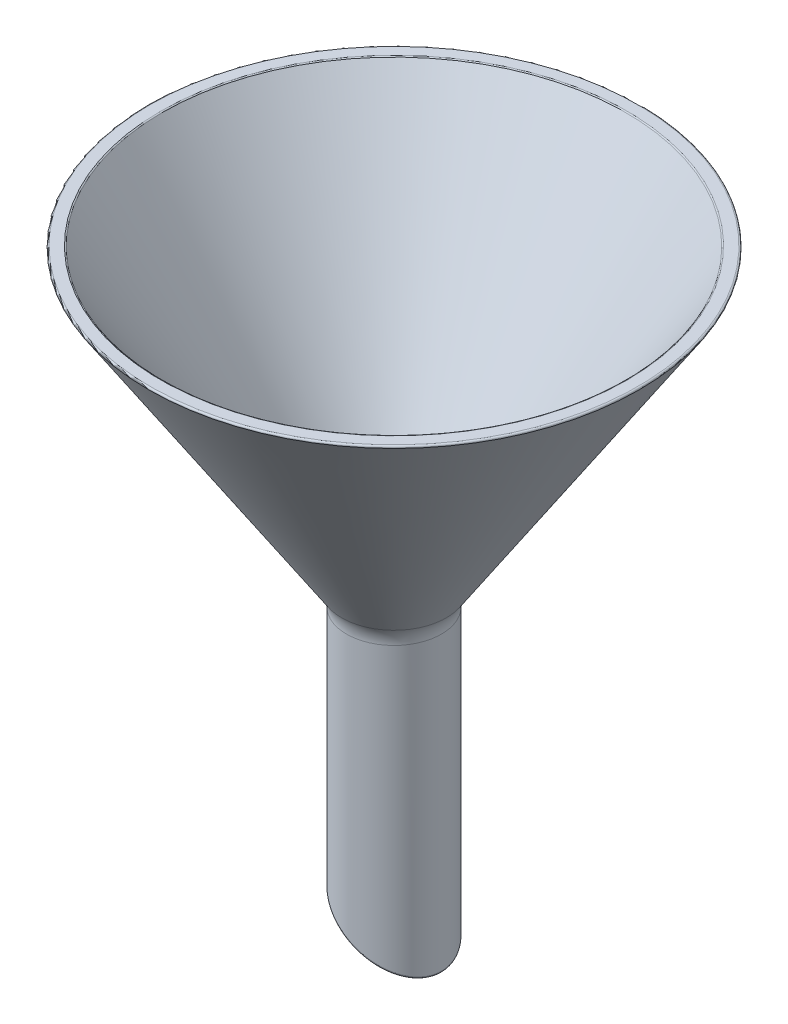
SolidWorks part; units mm, degrees
material "ABS"
ref_plane "Front" through (0, 0, 0) normal (0, 0, 1) x (1, 0, 0)
ref_plane "Top" through (0, 0, 0) normal (0, 1, 0) x (1, 0, 0)
ref_plane "Right" through (0, 0, 0) normal (1, 0, 0) x (0, 0, -1)
sketch "Sketch1" plane through (0, 0, 0) normal (0, 0, 1) x (1, 0, 0)
  line L0 (0, 0) -> (0, -52.07)
  line L1 (0, 0) -> (-20.6375, 0)
  line L2 (-20.6375, 0) -> (-3.9687, -25.4)
  line L3 (-3.9687, -25.4) -> (-3.9687, -52.07)
  line L4 (-3.9687, -52.07) -> (0, -52.07)
  point P3 (-4.952, -18.6192)
  dimension "D1" = 20.6375
  dimension "D2" = 52.07
  dimension "D3" = 26.67
  dimension "D4" = 3.9688
revolve "Revolve1" add sketch "Sketch1" angle 360 about L0
shell "Shell1" thickness 1.016 removed face at (-20.6375, 0, 0)
sketch "Sketch2" plane through (0, 0, 0) normal (0, 0, 1) x (1, 0, 0)
  line L0 (-3.9687, -45.72) -> (3.9688, -50.8)
  line L1 (-3.9687, -25.4) -> (-3.9687, -52.07) construction
  line L2 (3.9688, -52.07) -> (3.9688, -25.4) construction
  line L3 (3.9688, -50.8) -> (3.9688, -52.07)
  line L4 (3.9688, -52.07) -> (-3.9687, -52.07)
  line L5 (-3.9687, -52.07) -> (-3.9687, -45.72)
  dimension "D1" = 1.27
  dimension "D2" = 6.35
extrude "Cut-Extrude1" cut sketch "Sketch2" against normal through all and the other way through all
fillet "Fillet1" radius 2.54 2 edges at (-2.9527, -25.0964, 0) (-3.9687, -25.4, 0)
fillet "Fillet2" radius 0.127 4 edges at (-2.9527, -46.3702, 0) (-3.9687, -45.72, 0) (-19.4223, 0, 0) (-20.6375, 0, 0)
